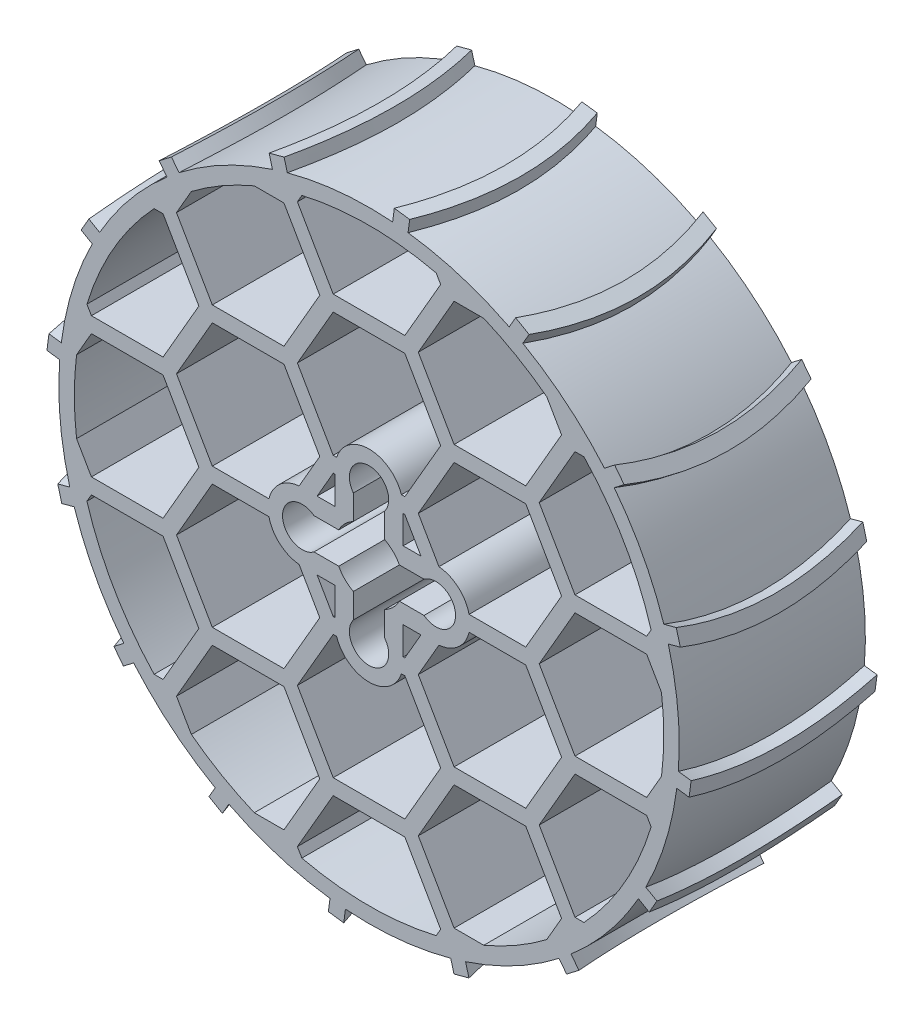
SolidWorks part; units mm, degrees
note: The reader was unsure of these and kept them because the rebuilt part matched: shared geometry of "Sketch1<4>", "Sketch1<6>", "Sketch1<7>".
ref_plane "Front Plane" through (0, 0, 0) normal (0, 0, 1) x (1, 0, 0)
ref_plane "Top Plane" through (0, 0, 0) normal (0, 1, 0) x (1, 0, 0)
ref_plane "Right Plane" through (0, 0, 0) normal (1, 0, 0) x (0, 0, -1)
sketch "Sketch1" plane through (0, 0, 0) normal (0, 0, 1) x (1, 0, 0)
  line L0 (-23.094, 45) -> (-11.547, 25)
  line L2 (-11.547, -20) -> (-11, -20)
  line L3 (11.547, -20) -> (16.7432, -11)
  line L4 (17.3205, 10) -> (17.2484, 10.1249)
  line L5 (11.547, 20) -> (11, 20)
  line L6 (-11.547, 20) -> (-16.7432, 11)
  line L7 (-11.547, 25) -> (-10.4443, 25)
  line L8 (11.547, 25) -> (23.094, 45)
  line L9 (23.094, 45) -> (11.547, 65)
  line L10 (11.547, 65) -> (-11.547, 65)
  line L11 (-11.547, 65) -> (-23.094, 45)
  line L12 (-23.094, 90) -> (-11.547, 70)
  line L13 (-11.547, 70) -> (11.547, 70)
  line L14 (11.547, 70) -> (23.094, 90)
  line L15 (23.094, 90) -> (21.6506, 92.5)
  line L17 (-21.6506, 92.5) -> (-23.094, 90)
  line L18 (-23.094, -45) -> (-11.547, -65)
  line L19 (-11.547, -65) -> (11.547, -65)
  line L20 (11.547, -65) -> (23.094, -45)
  line L21 (23.094, -45) -> (11.547, -25)
  line L22 (11.547, -25) -> (10.4443, -25)
  line L23 (-11.547, -25) -> (-23.094, -45)
  line L24 (-23.094, -90) -> (-21.6506, -92.5)
  line L26 (21.6506, -92.5) -> (23.094, -90)
  line L27 (23.094, -90) -> (11.547, -70)
  line L28 (11.547, -70) -> (-11.547, -70)
  line L29 (-11.547, -70) -> (-23.094, -90)
  line L30 (15.8771, 22.5) -> (22.5427, 10.9549)
  line L31 (32.2601, 2.5) -> (50.5181, 2.5)
  line L32 (50.5181, 2.5) -> (62.0652, 22.5)
  line L33 (62.0652, 22.5) -> (50.5181, 42.5)
  line L34 (50.5181, 42.5) -> (27.4241, 42.5)
  line L35 (27.4241, 42.5) -> (15.8771, 22.5)
  line L36 (22.5427, -10.9549) -> (15.8771, -22.5)
  line L37 (15.8771, -22.5) -> (27.4241, -42.5)
  line L38 (27.4241, -42.5) -> (50.5181, -42.5)
  line L39 (50.5181, -42.5) -> (62.0652, -22.5)
  line L40 (62.0652, -22.5) -> (50.5181, -2.5)
  line L41 (50.5181, -2.5) -> (32.2601, -2.5)
  line L42 (11.547, -25) -> (10.4443, -25)
  line L43 (-11.547, -25) -> (-23.094, -45)
  line L44 (-23.094, -45) -> (-11.547, -65)
  line L45 (-11.547, -65) -> (11.547, -65)
  line L46 (11.547, -65) -> (23.094, -45)
  line L47 (23.094, -45) -> (11.547, -25)
  line L48 (-15.8771, -22.5) -> (-22.5427, -10.9549)
  line L49 (-32.2601, -2.5) -> (-50.5181, -2.5)
  line L50 (-50.5181, -2.5) -> (-62.0652, -22.5)
  line L51 (-62.0652, -22.5) -> (-50.5181, -42.5)
  line L52 (-50.5181, -42.5) -> (-27.4241, -42.5)
  line L53 (-27.4241, -42.5) -> (-15.8771, -22.5)
  line L54 (-22.5427, 10.9549) -> (-15.8771, 22.5)
  line L55 (-15.8771, 22.5) -> (-27.4241, 42.5)
  line L56 (-27.4241, 42.5) -> (-50.5181, 42.5)
  line L57 (-50.5181, 42.5) -> (-62.0652, 22.5)
  line L58 (-62.0652, 22.5) -> (-50.5181, 2.5)
  line L59 (-50.5181, 2.5) -> (-32.2601, 2.5)
  line L60 (-11.547, 25) -> (-10.4443, 25)
  line L61 (11.547, 25) -> (23.094, 45)
  line L62 (23.094, 45) -> (11.547, 65)
  line L63 (11.547, 65) -> (-11.547, 65)
  line L64 (-11.547, 65) -> (-23.094, 45)
  line L65 (-23.094, 45) -> (-11.547, 25)
  line L66 (-27.4241, 47.5) -> (-15.8771, 67.5)
  line L67 (-15.8771, 67.5) -> (-27.4241, 87.5)
  line L68 (-27.4241, 87.5) -> (-36.9966, 87.5)
  line L69 (-57.2789, 75.79) -> (-62.0652, 67.5)
  line L70 (-62.0652, 67.5) -> (-50.5181, 47.5)
  line L71 (-50.5181, 47.5) -> (-27.4241, 47.5)
  line L72 (-15.8771, -67.5) -> (-27.4241, -47.5)
  line L73 (-27.4241, -47.5) -> (-50.5181, -47.5)
  line L74 (-50.5181, -47.5) -> (-62.0652, -67.5)
  line L75 (-62.0652, -67.5) -> (-57.2789, -75.79)
  line L76 (-36.9966, -87.5) -> (-27.4241, -87.5)
  line L77 (-27.4241, -87.5) -> (-15.8771, -67.5)
  line L78 (-66.3953, 25) -> (-54.8483, 45)
  line L79 (-54.8483, 45) -> (-66.3953, 65)
  line L80 (-66.3953, 65) -> (-69.282, 65)
  line L82 (-90.9327, 27.5) -> (-89.4893, 25)
  line L83 (-89.4893, 25) -> (-66.3953, 25)
  line L84 (-66.3953, -20) -> (-54.8483, 0)
  line L85 (-54.8483, 0) -> (-66.3953, 20)
  line L86 (-66.3953, 20) -> (-89.4893, 20)
  line L87 (-89.4893, 20) -> (-94.2755, 11.71)
  line L88 (-94.2755, -11.71) -> (-89.4893, -20)
  line L89 (-89.4893, -20) -> (-66.3953, -20)
  line L90 (-66.3953, -65) -> (-54.8483, -45)
  line L91 (-54.8483, -45) -> (-66.3953, -25)
  line L92 (-66.3953, -25) -> (-89.4893, -25)
  line L93 (-89.4893, -25) -> (-90.9327, -27.5)
  line L95 (-69.282, -65) -> (-66.3953, -65)
  line L96 (15.8771, 67.5) -> (27.4241, 47.5)
  line L97 (27.4241, 47.5) -> (50.5181, 47.5)
  line L98 (50.5181, 47.5) -> (62.0652, 67.5)
  line L99 (62.0652, 67.5) -> (57.2789, 75.79)
  line L100 (36.9966, 87.5) -> (27.4241, 87.5)
  line L101 (27.4241, 87.5) -> (15.8771, 67.5)
  line L102 (27.4241, -47.5) -> (15.8771, -67.5)
  line L103 (15.8771, -67.5) -> (27.4241, -87.5)
  line L104 (27.4241, -87.5) -> (36.9966, -87.5)
  line L105 (57.2789, -75.79) -> (62.0652, -67.5)
  line L106 (62.0652, -67.5) -> (50.5181, -47.5)
  line L107 (50.5181, -47.5) -> (27.4241, -47.5)
  line L108 (66.3953, -25) -> (54.8483, -45)
  line L109 (54.8483, -45) -> (66.3953, -65)
  line L110 (66.3953, -65) -> (69.282, -65)
  line L112 (90.9327, -27.5) -> (89.4893, -25)
  line L113 (89.4893, -25) -> (66.3953, -25)
  line L114 (66.3953, 20) -> (54.8483, 0)
  line L115 (54.8483, 0) -> (66.3953, -20)
  line L116 (66.3953, -20) -> (89.4893, -20)
  line L117 (89.4893, -20) -> (94.2755, -11.71)
  line L118 (94.2755, 11.71) -> (89.4893, 20)
  line L119 (89.4893, 20) -> (66.3953, 20)
  line L120 (66.3953, 65) -> (54.8483, 45)
  line L121 (54.8483, 45) -> (66.3953, 25)
  line L122 (66.3953, 25) -> (89.4893, 25)
  line L123 (89.4893, 25) -> (90.9327, 27.5)
  line L125 (69.282, 65) -> (66.3953, 65)
  line L126 (-11.547, -110) -> (11.547, -110) [skipped]
  line L127 (89.4893, -65) -> (101.0363, -45) [skipped]
  line L128 (101.0363, 45) -> (89.4893, 65) [skipped]
  line L129 (11.547, 110) -> (-11.547, 110) [skipped]
  line L130 (-89.4893, 65) -> (-101.0363, 45) [skipped]
  line L131 (-101.0363, -45) -> (-89.4893, -65) [skipped]
  line L132 (11, -20) -> (11.547, -20)
  line L133 (-11, 20) -> (-11.547, 20)
  line L134 (-10.4443, -25) -> (-11.547, -25)
  line L135 (-10.4443, -25) -> (-11.547, -25)
  line L136 (10.4443, 25) -> (11.547, 25)
  line L137 (10.4443, 25) -> (11.547, 25)
  line L138 (-5.0583, 17.7275) -> (-5.0583, 9.768)
  line L139 (5.0583, 17.7275) -> (5.0583, 9.768)
  line L140 (17.7275, 5.0583) -> (9.768, 5.0583)
  line L141 (17.7275, -5.0583) -> (9.768, -5.0583)
  line L142 (5.0583, -17.7275) -> (5.0583, -9.768)
  line L143 (-5.0583, -17.7275) -> (-5.0583, -9.768)
  line L144 (-17.7275, -5.0583) -> (-9.768, -5.0583)
  line L145 (-17.7275, 5.0583) -> (-9.768, 5.0583)
  line L146 (-21.548, 11) -> (-11, 11)
  line L147 (-11, 21.548) -> (-11, 11)
  line L148 (16.7432, 11) -> (11.547, 20)
  line L149 (21.548, 11) -> (11, 11)
  line L150 (11, 21.548) -> (11, 11)
  line L151 (11, -21.548) -> (11, -11)
  line L152 (21.548, -11) -> (11, -11)
  line L153 (-21.548, -11) -> (-11, -11)
  line L154 (-11, -21.548) -> (-11, -11)
  line L155 (-16.7432, -11) -> (-11.547, -20)
  line L156 (-17.3205, -10) -> (-17.2484, -10.1249) [skipped]
  line L157 (27.4241, 42.5) -> (50.5181, 2.5) construction
  circle A0 centre (0, 0) radius 100
  arc A1 (9.768, 5.0583) -> (5.0583, 9.768) centre (0, 0) ccw
  arc A3 (-9.768, -5.0583) -> (-5.0583, -9.768) centre (0, 0) ccw
  arc A5 (21.548, -11) -> (21.548, 11) centre (21.548, 0) ccw
  arc A6 (-11, -21.548) -> (11, -21.548) centre (0, -21.548) ccw
  arc A7 (-21.548, 11) -> (-21.548, -11) centre (-21.548, 0) ccw
  arc A8 (11, 21.548) -> (-11, 21.548) centre (0, 21.548) ccw
  arc A9 (-5.0583, 9.768) -> (-9.768, 5.0583) centre (0, 0) ccw
  arc A10 (5.0583, -9.768) -> (9.768, -5.0583) centre (0, 0) ccw
  arc A11 (17.2484, 10.1249) -> (17.2479, 10.1247) centre (21.548, 0) ccw
  circle A12 centre (0, 0) radius 95
  arc A14 (17.3205, 10) -> (17.2479, 10.1247) centre (0, 0) ccw construction
  circle A15 centre (0, 21.548) radius 3.302
  circle A16 centre (21.548, 0) radius 3.302
  circle A17 centre (0, -21.548) radius 3.302
  circle A18 centre (-21.548, 0) radius 3.302
  circle A19 centre (0, 21.548) radius 6.339
  circle A20 centre (21.548, 0) radius 6.339
  circle A21 centre (0, -21.548) radius 6.339
  circle A22 centre (-21.548, 0) radius 6.339
  arc A26 (0.6006, 18.3011) -> (-0.6006, 18.3011) centre (0, 0) ccw
  point P72 (0, 0)
  point P162 (0, 0)
  point P195 (0, 0)
  point P203 (0, 0)
  point P221 (0, 0)
  point P237 (0, 0)
  dimension "D15" = 2
  dimension "D19" = 10.548
  dimension "D20" = 4
  dimension "D21" = 4
  dimension "D22" = 4
  dimension "D24" = 11
  dimension "D25" = 12.678
  dimension "D26" = 6.604
  dimension "D27" = 10.548
  dimension "D28" = 200
  dimension "D29" = 190
  dimension "D5" = 5
  dimension "D17" = 5
  dimension "D18" = 5
  dimension "D30" = 7.9595
  dimension "D31" = 5
  dimension "D32" = 5
  dimension "D33" = 5
  dimension "D34" = 5
  dimension "D35" = 5
  dimension "D36" = 5
  dimension "D37" = 5
  dimension "D2" = 3
  dimension "D3" = 3
  dimension "D4" = 2
  dimension "D7" = 2
  dimension "D8" = 2
  dimension "D9" = 2
  dimension "D10" = 3
  dimension "D11" = 2
  dimension "D12" = 2
  dimension "D13" = 2
  dimension "D14" = 3
  dimension "D6" = 6
  dimension "D16" = 4
  dimension "D23" = 4
extrude "Boss-Extrude1" add sketch "Sketch1" along normal blind 60
extrude "Boss-Extrude2" add sketch "Sketch1<4>" along normal blind 10 contours A19 A15 | A20 A16 | A22 A18 | A21 A17
sketch "Sketch1<4>" plane through (0, 0, 0) normal (0, 0, 1) x (1, 0, 0) same geometry as "Sketch1"
extrude "Boss-Extrude4" add sketch "Sketch1<6>" along normal blind 30 contours A21 A17 | A22 A18 | A20 A16 | A19 A15
sketch "Sketch1<6>" plane through (0, 0, 0) normal (0, 0, 1) x (1, 0, 0) same geometry as "Sketch1"
extrude "Boss-Extrude5" add sketch "Sketch1<7>" along normal blind 60 contours A0 A12
sketch "Sketch1<7>" plane through (0, 0, 0) normal (0, 0, 1) x (1, 0, 0) same geometry as "Sketch1"
ref_plane "Plane1" through (50, 86.6025, 0) normal (0.5, 0.866, 0) x (0.866, -0.5, 0)
sketch "Sketch2" plane through (50, 86.6025, 0) normal (0.5, 0.866, 0) x (0.866, -0.5, 0)
  line L0 (0, 0) -> (-0.4737, -60)
  line L1 (-0.2369, -30) -> (4.7631, -30)
  line L2 (0, 0) -> (-5, 0)
  line L3 (-0.4737, -60) -> (-5.4737, -60)
  spline S0 degree 2 poles (0, 0) (9.7625, -30.0768) (-0.4737, -60) knots 0 0 0 1 1 1
  spline S1 degree 2 poles (-5, 0) (4.7625, -30.0768) (-5.4737, -60) knots 0 0 0 1 1 1
  point P4 (-0.2369, -30)
  dimension "D1" = 5
extrude "Boss-Extrude6" add sketch "Sketch2" along normal blind 4 and the other way blind 2 contours L2 S1 L0 | S0 L0 L1 | S0 L1 L0 | L0 S1 L3
pattern_circular "CirPattern3" count 16 over 360 about axis through (0, 0, 60) along (0, 0, -1) of "Boss-Extrude6"
